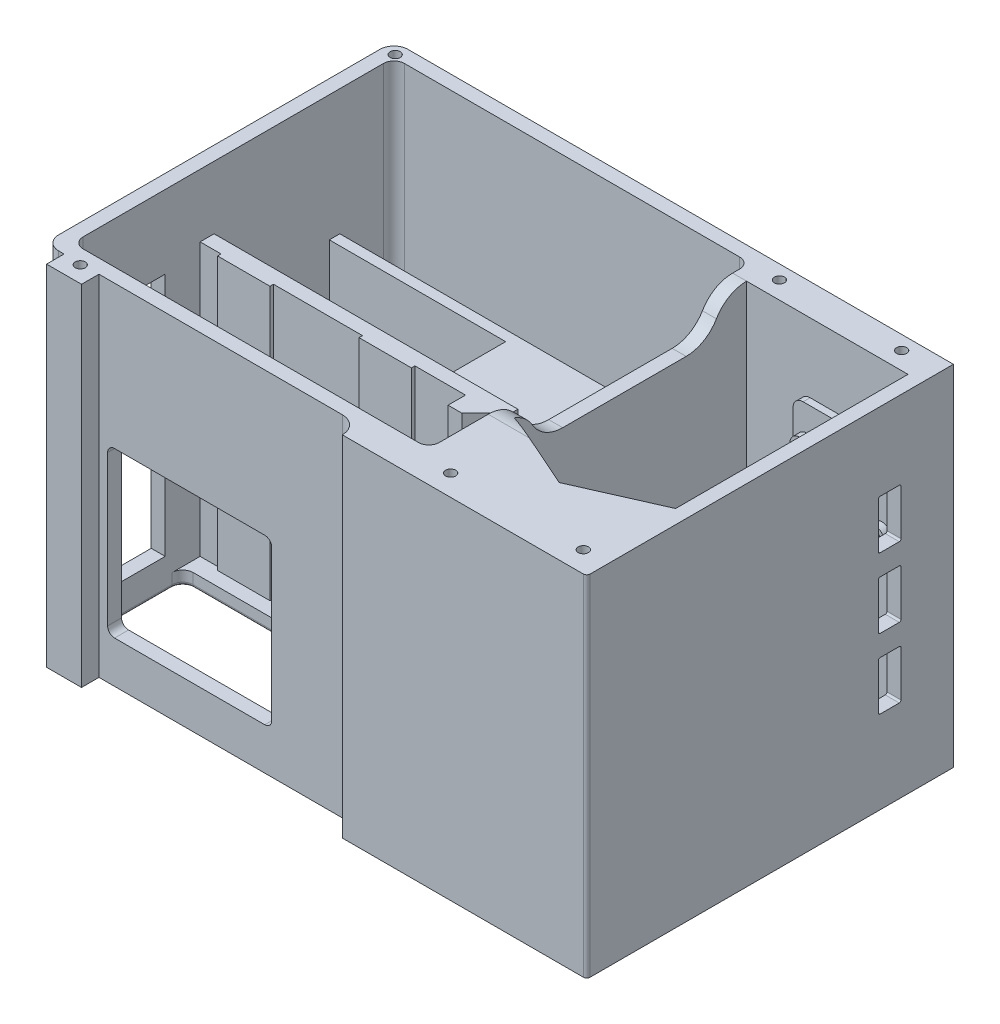
SolidWorks part; units mm, degrees
ref_plane "前视基准面" through (0, 0, 0) normal (0, 0, 1) x (1, 0, 0)
ref_plane "上视基准面" through (0, 0, 0) normal (0, 1, 0) x (1, 0, 0)
ref_plane "右视基准面" through (0, 0, 0) normal (1, 0, 0) x (0, 0, -1)
sketch "草图2" plane through (0, 0, 0) normal (0, 1, 0) x (1, 0, 0)
  line L1 (-51, 50) -> (51, 50)
  line L2 (-55, 46) -> (-55, -46)
  line L3 (-51, -50) -> (51, -50)
  line L4 (55, 46) -> (55, -46)
  line L5 (-55, 50) -> (55, -50) construction
  line L6 (-55, -50) -> (55, 50) construction
  arc A0 (51, 50) -> (55, 46) centre (51, 46) cw
  arc A1 (-55, -46) -> (-51, -50) centre (-51, -46) ccw
  arc A2 (-51, 50) -> (-55, 46) centre (-51, 46) ccw
  arc A3 (51, -50) -> (55, -46) centre (51, -46) ccw
  point P0 (0, 0)
  dimension "D3" = 4
  dimension "D1" = 100
  dimension "D2" = 110
extrude "凸台-拉伸1" add sketch "草图2" along normal blind 100
shell "抽壳1" thickness 4 removed face at (0, 100, 0)
sketch "草图3" plane through (0, 0, 0) normal (0, -1, 0) x (1, 0, 0)
  line L0 (-51, 50) -> (51, 50) construction
  line L1 (-48, 40) -> (11, 40)
  line L2 (-51, 37) -> (-51, 17.5)
  line L3 (-48, 14.5) -> (11, 14.5)
  line L4 (14, 37) -> (14, 17.5)
  line L5 (-55, -46) -> (-55, 46) construction
  arc A0 (11, 40) -> (14, 37) centre (11, 37) cw
  arc A1 (-51, 17.5) -> (-48, 14.5) centre (-48, 17.5) ccw
  arc A2 (11, 14.5) -> (14, 17.5) centre (11, 17.5) ccw
  arc A3 (-48, 40) -> (-51, 37) centre (-48, 37) ccw
  point P6 (14, 40)
  point P9 (-51, 14.5)
  point P14 (-51, 40)
  dimension "D3" = 3
  dimension "D1" = 25.5
  dimension "D2" = 65
  dimension "D4" = 10
  dimension "D5" = 4
extrude "切除-拉伸1" cut sketch "草图3" against normal up to next
sketch "草图4" plane through (0, 0, 0) normal (0, -1, 0) x (1, 0, 0)
  line L4 (11, 40) -> (46, 40)
  line L6 (11, 14.5) -> (46, 14.5)
  line L7 (49, 37) -> (49, 17.5)
  line L8 (55, 46) -> (55, -46) construction
  line L9 (14, 17.5) -> (14, 37) construction
  line L10 (14, 17.5) -> (14, 37)
  arc A0 (46, 40) -> (49, 37) centre (46, 37) cw
  arc A1 (46, 14.5) -> (49, 17.5) centre (46, 17.5) ccw
  arc A2 (14, 37) -> (11, 40) centre (11, 37) ccw construction
  arc A3 (14, 37) -> (11, 40) centre (11, 37) ccw
  arc A4 (11, 14.5) -> (14, 17.5) centre (11, 17.5) ccw construction
  arc A5 (11, 14.5) -> (14, 17.5) centre (11, 17.5) ccw
  dimension "D3" = 3
  dimension "D1" = 6
extrude "切除-拉伸2" cut sketch "草图4" against normal blind 2
sketch "草图5" plane through (0, 0, 0) normal (0, -1, 0) x (1, 0, 0)
  line L0 (3.5, -13) -> (48, -13)
  line L1 (-48, -13) -> (-3.5, -13)
  line L2 (-50, -15) -> (-50, -24.5)
  line L3 (-48, -26.5) -> (-3.5, -26.5)
  line L4 (-1.5, -15) -> (-1.5, -24.5)
  line L5 (1.5, -15) -> (1.5, -24.5)
  line L6 (3.5, -26.5) -> (48, -26.5)
  line L7 (50, -15) -> (50, -24.5)
  line L8 (-48, -31.5) -> (-3.5, -31.5)
  line L9 (-50, -33.5) -> (-50, -43)
  line L10 (-48, -45) -> (-3.5, -45)
  line L11 (-1.5, -33.5) -> (-1.5, -43)
  line L12 (3.5, -31.5) -> (48, -31.5)
  line L13 (1.5, -33.5) -> (1.5, -43)
  line L14 (3.5, -45) -> (48, -45)
  line L15 (50, -33.5) -> (50, -43)
  line L17 (51, -50) -> (-51, -50) construction
  line L18 (55, 46) -> (55, -46) construction
  line L21 (-55, -46) -> (-55, 46) construction
  arc A0 (48, -31.5) -> (50, -33.5) centre (48, -33.5) cw
  arc A1 (1.5, -43) -> (3.5, -45) centre (3.5, -43) ccw
  arc A2 (48, -45) -> (50, -43) centre (48, -43) ccw
  arc A3 (3.5, -31.5) -> (1.5, -33.5) centre (3.5, -33.5) ccw
  arc A4 (-3.5, -31.5) -> (-1.5, -33.5) centre (-3.5, -33.5) cw
  arc A5 (-50, -43) -> (-48, -45) centre (-48, -43) ccw
  arc A6 (-3.5, -45) -> (-1.5, -43) centre (-3.5, -43) ccw
  arc A7 (-48, -31.5) -> (-50, -33.5) centre (-48, -33.5) ccw
  arc A8 (48, -13) -> (50, -15) centre (48, -15) cw
  arc A9 (1.5, -24.5) -> (3.5, -26.5) centre (3.5, -24.5) ccw
  arc A10 (48, -26.5) -> (50, -24.5) centre (48, -24.5) ccw
  arc A11 (3.5, -13) -> (1.5, -15) centre (3.5, -15) ccw
  arc A12 (-3.5, -13) -> (-1.5, -15) centre (-3.5, -15) cw
  arc A13 (-50, -24.5) -> (-48, -26.5) centre (-48, -24.5) ccw
  arc A14 (-3.5, -26.5) -> (-1.5, -24.5) centre (-3.5, -24.5) ccw
  arc A15 (-48, -13) -> (-50, -15) centre (-48, -15) ccw
  point P42 (-1.5, -13)
  point P45 (-50, -26.5)
  point P50 (-50, -13)
  dimension "D3" = 2
  dimension "D1" = 13.5
  dimension "D2" = 48.5
  dimension "D4" = 5
  dimension "D5" = 5
  dimension "D6" = 5
  dimension "D7" = 5
extrude "切除-拉伸3" cut sketch "草图5" against normal up to next
fillet "圆角1" radius 3 4 edges at (-51, 52, -46) (-51, 52, 46) (51, 52, 46) (51, 52, -46)
sketch "草图6" plane through (0, 4, 0) normal (0, 1, 0) x (1, 0, 0)
  line L0 (51, -43) -> (51, 43) construction
  line L1 (-51, -5.5) -> (51, -5.5)
  line L2 (-51, -5.5) -> (-51, -9.5)
  line L3 (-51, -9.5) -> (51, -9.5)
  line L4 (51, -5.5) -> (51, -9.5)
  line L5 (-51, 43) -> (-51, -43) construction
  line L7 (-48, -46) -> (48, -46) construction
  dimension "D1" = 4
  dimension "D2" = 0
  dimension "D3" = 0
  dimension "D4" = 36.5
extrude "凸台-拉伸2" add sketch "草图6" along normal blind 78
sketch "草图7" plane through (0, 4, 0) normal (0, 1, 0) x (1, 0, 0)
  line L0 (-51, -9.5) -> (51, -9.5) construction
  line L1 (-30, -9.5) -> (-45, -9.5)
  line L2 (-30, -9.5) -> (-30, -10.5)
  line L3 (-30, -10.5) -> (-45, -10.5)
  line L4 (-45, -9.5) -> (-45, -10.5)
  line L6 (-48, -46) -> (48, -46) construction
  line L7 (-51, 43) -> (-51, -43) construction
  dimension "D1" = 35.5
  dimension "D2" = 15
  dimension "D3" = 6
extrude "凸台-拉伸3" add sketch "草图7" along normal up to surface (78 mm away) up to face at (0, 82, 7.5)
sketch "草图9" plane through (0, 4, 0) normal (0, 1, 0) x (1, 0, 0)
  line L0 (-30, -9.5) -> (51, -9.5) construction
  line L1 (10.5, -9.5) -> (-4.5, -9.5)
  line L2 (10.5, -9.5) -> (10.5, -10.5)
  line L3 (10.5, -10.5) -> (-4.5, -10.5)
  line L4 (-4.5, -9.5) -> (-4.5, -10.5)
  line L5 (-45, -10.5) -> (-30, -10.5) construction
  dimension "D1" = 15
extrude "凸台-拉伸4" add sketch "草图9" along normal up to surface (78 mm away) up to face at (-18.75, 82, 8.75)
sketch "草图10" plane through (0, 4, 0) normal (0, 1, 0) x (1, 0, 0)
  line L0 (10.5, -9.5) -> (51, -9.5) construction
  line L1 (29, -9.5) -> (25, -9.5)
  line L3 (29, -14.5) -> (25, -14.5)
  line L4 (25, -9.5) -> (25, -14.5)
  line L5 (-51, 43) -> (-51, -43) construction
  line L6 (29, -14.5) -> (34, -9.5)
  line L7 (34, -9.5) -> (29, -9.5)
  dimension "D1" = 76
  dimension "D2" = 5
  dimension "D3" = 4
extrude "凸台-拉伸5" add sketch "草图10" along normal up to surface (78 mm away) up to face at (-11.5, 82, 9.1667)
sketch "草图13" plane through (0, 0, 5.5) normal (0, 0, -1) x (-1, 0, 0)
  line L0 (-36, 82) -> (-36, 62)
  line L1 (-36, 62) -> (-51, 62)
  line L4 (-51, 4) -> (51, 4)
  line L5 (51, 4) -> (51, 82)
  line L6 (51, 82) -> (-51, 82)
  line L7 (-51, 82) -> (-51, 4)
  line L10 (-36, 82) -> (-51, 82)
  line L11 (-51, 82) -> (-51, 62)
  dimension "D2" = 15
  dimension "D3" = 20
  dimension "D1" = 0
extrude "切除-拉伸4" cut sketch "草图13" against normal up to next
sketch "草图15" plane through (0, 4, 0) normal (0, 1, 0) x (1, 0, 0)
  line L0 (-51, 43) -> (-51, -43) construction
  line L1 (-51, 30.5) -> (52.1172, 30.5)
  line L2 (-51, 30.5) -> (-51, 27.5)
  line L3 (-51, 27.5) -> (52.1172, 27.5)
  line L4 (52.1172, 30.5) -> (52.1172, 27.5)
  line L5 (48, 46) -> (-48, 46) construction
  line L7 (48, 26.5) -> (3.5, 26.5) construction
  dimension "D1" = 15.5
  dimension "D2" = 1
extrude "凸台-拉伸7" add sketch "草图15" along normal blind 60
sketch "草图16" plane through (0, 4, 0) normal (0, 1, 0) x (1, 0, 0)
  line L6 (36, -5.5) -> (-51, -5.5) construction
  line L7 (-0.5, -5.5) -> (1.5, -5.5)
  line L8 (-0.5, -5.5) -> (-0.5, 27.5)
  line L9 (-0.5, 27.5) -> (1.5, 27.5)
  line L10 (1.5, -5.5) -> (1.5, 27.5)
  line L11 (-51, 27.5) -> (51, 27.5) construction
  line L12 (-51, 43) -> (-51, -43) construction
  line L13 (1.5, 24.5) -> (1.5, 15) construction
  dimension "D1" = 50.5
extrude "凸台-拉伸8" add sketch "草图16" along normal up to surface (60 mm away) up to face at (0, 64, -29)
sketch "草图17" plane through (0, 4, 0) normal (0, 1, 0) x (1, 0, 0)
  line L0 (-0.5, 27.5) -> (-0.5, -5.5) construction
  line L1 (-51, -5.5) -> (-0.5, -5.5)
  line L2 (-51, -5.5) -> (-51, 11.6)
  line L3 (-51, 11.6) -> (-0.5, 11.6)
  line L4 (-0.5, -5.5) -> (-0.5, 11.6)
  line L5 (-51, 27.5) -> (-0.5, 27.5) construction
  dimension "D1" = 15.9
extrude "凸台-拉伸9" add sketch "草图17" along normal up to surface (60 mm away) up to face at (0.25, 64, -20)
sketch "草图18" plane through (0, 0, 50) normal (0, 0, 1) x (1, 0, 0)
  line L0 (-55, 100) -> (-55, 0) construction
  line L1 (-35, 59) -> (8, 59)
  line L2 (-37, 57) -> (-37, 14)
  line L3 (-35, 12) -> (8, 12)
  line L4 (10, 57) -> (10, 14)
  line L5 (-51, 0) -> (51, 0) construction
  arc A0 (8, 59) -> (10, 57) centre (8, 57) cw
  arc A1 (-37, 14) -> (-35, 12) centre (-35, 14) ccw
  arc A2 (8, 12) -> (10, 14) centre (8, 14) ccw
  arc A3 (-35, 59) -> (-37, 57) centre (-35, 57) ccw
  point P10 (10, 59)
  point P15 (10, 12)
  point P18 (-37, 59)
  dimension "D5" = 2
  dimension "D1" = 47
  dimension "D2" = 47
  dimension "D3" = 18
  dimension "D4" = 12
extrude "切除-拉伸5" cut sketch "草图18" against normal up to next
sketch "草图19" plane through (-55, 0, 0) normal (-1, 0, 0) x (0, 0, 1)
  line L1 (19.5, 9) -> (41.5, 9)
  line L2 (19.5, 9) -> (19.5, 79)
  line L3 (19.5, 79) -> (41.5, 79)
  line L4 (41.5, 9) -> (41.5, 79)
  line L5 (-46, 0) -> (46, 0) construction
  line L7 (50, 100) -> (50, 0) construction
  dimension "D1" = 70
  dimension "D2" = 22
  dimension "D3" = 9
  dimension "D4" = 8.5
extrude "切除-拉伸6" cut sketch "草图19" against normal up to next
sketch "草图20" plane through (0, 4, 0) normal (0, 1, 0) x (1, 0, 0)
  line L0 (-48, -46) -> (48, -46) construction
  line L1 (12.1183, -46) -> (18.3326, -46)
  line L2 (12.1183, -46) -> (12.1183, -44.4)
  line L3 (12.1183, -44.4) -> (18.3326, -44.4)
  line L4 (18.3326, -46) -> (18.3326, -44.4)
  line L6 (-48, -46) -> (-43.8248, -46)
  line L7 (-48, -46) -> (-48, -44.4)
  line L8 (-48, -44.4) -> (-43.8248, -44.4)
  line L9 (-43.8248, -46) -> (-43.8248, -44.4)
  line L13 (-4.5, -10.5) -> (10.5, -10.5) construction
  line L14 (-45, -10.5) -> (-30, -10.5) construction
  dimension "D1" = 33.9
  dimension "D2" = 33.9
extrude "凸台-拉伸10" add sketch "草图20" along normal up to surface (78 mm away) up to face at (-3.4375, 82, 9.875)
sketch "草图21" plane through (0, 4, 0) normal (0, 1, 0) x (1, 0, 0)
  line L0 (1.5, 11.6) -> (51, 11.6)
  line L1 (1.5, -5.5) -> (1.5, 27.5) construction
  line L2 (1.5, -5.5) -> (1.5, 27.5)
  line L3 (36, -5.5) -> (-51, -5.5) construction
  line L4 (36, -5.5) -> (1.5, -5.5)
  line L5 (51, -5.5) -> (1.5, -5.5) construction
  line L6 (51, -5.5) -> (1.5, -5.5)
  line L7 (51, -5.5) -> (51, 27.5) construction
  line L8 (1.5, 15) -> (1.5, -5.5)
  line L9 (1.5, -5.5) -> (51, -5.5)
  line L10 (51, -5.5) -> (51, 27.5)
  line L11 (51, 27.5) -> (1.5, 27.5)
  line L12 (1.5, 27.5) -> (1.5, 24.5)
  line L13 (3.5, 26.5) -> (48, 26.5)
  line L14 (50, 24.5) -> (50, 15)
  line L15 (48, 13) -> (3.5, 13)
  line L16 (1.5, 15) -> (1.5, 11.6)
  line L18 (51, 11.6) -> (51, 27.5)
  line L19 (51, 27.5) -> (1.5, 27.5)
  line L20 (1.5, 27.5) -> (1.5, 24.5)
  line L21 (3.5, 26.5) -> (48, 26.5)
  line L22 (50, 24.5) -> (50, 15)
  line L23 (48, 13) -> (3.5, 13)
  line L24 (51, -5.5) -> (51, 27.5)
  arc A4 (3.5, 26.5) -> (1.5, 24.5) centre (3.5, 24.5) ccw
  arc A5 (50, 24.5) -> (48, 26.5) centre (48, 24.5) ccw
  arc A6 (48, 13) -> (50, 15) centre (48, 15) ccw
  arc A7 (1.5, 15) -> (3.5, 13) centre (3.5, 15) ccw
  arc A8 (3.5, 26.5) -> (1.5, 24.5) centre (3.5, 24.5) ccw
  arc A9 (50, 24.5) -> (48, 26.5) centre (48, 24.5) ccw
  arc A10 (48, 13) -> (50, 15) centre (48, 15) ccw
  arc A11 (1.5, 15) -> (3.5, 13) centre (3.5, 15) ccw
  line M14 (1.5, 15) -> (1.5, -5.5)
  line M15 (1.5, -5.5) -> (51, -5.5)
  line M16 (51, -5.5) -> (51, 27.5)
  line M17 (51, 27.5) -> (1.5, 27.5)
  line M18 (1.5, 27.5) -> (1.5, 24.5)
  arc M19 (1.5, 24.5) -> (3.5, 26.5) centre (3.5, 24.5) cw
  line M20 (3.5, 26.5) -> (48, 26.5)
  arc M21 (48, 26.5) -> (50, 24.5) centre (48, 24.5) cw
  line M22 (50, 24.5) -> (50, 15)
  arc M23 (50, 15) -> (48, 13) centre (48, 15) cw
  line M24 (48, 13) -> (3.5, 13)
  arc M25 (3.5, 13) -> (1.5, 15) centre (3.5, 15) cw
  dimension "D1" = 0
extrude "凸台-拉伸11" add sketch "草图21" along normal up to surface (60 mm away) contours L0 M14 M15 M16 | L0 M14 M16 M17 M18 M19 M20 M21 M22 M23 M24 M25 region at (2.0199, 4, -13.3) region at (26.25, 4, -3.05) up to face at (-10, 64, -18.32)
fillet "圆角2" radius 3 1 edges at (43.5, 62, 5.5)
fillet "圆角3" radius 3 1 edges at (43.5, 64, 5.5)
sketch "草图22" plane through (0, 0, 0) normal (0, -1, 0) x (1, 0, 0)
  line L0 (51, 50) -> (105.215, 50)
  line L1 (105.215, 50) -> (105.215, -50)
  line L2 (105.215, -50) -> (51, -50)
  line L4 (55, -46) -> (55, 46)
  line L5 (51, 50) -> (-51, 50)
  line L6 (-55, 46) -> (-55, -46)
  line L7 (-51, -50) -> (51, -50)
  line L8 (55, -46) -> (55, 46)
  arc A4 (51, -50) -> (55, -46) centre (51, -46) ccw
  arc A5 (55, 46) -> (51, 50) centre (51, 46) ccw
  arc A6 (-51, 50) -> (-55, 46) centre (-51, 46) ccw
  arc A7 (-55, -46) -> (-51, -50) centre (-51, -46) ccw
  arc A8 (51, -50) -> (55, -46) centre (51, -46) ccw
  arc A9 (55, 46) -> (51, 50) centre (51, 46) ccw
  dimension "D1" = 0
extrude "凸台-拉伸12" add sketch "草图22" against normal up to surface (100 mm away) up to face at (0, 100, 0)
sketch "草图23" plane through (0, 0, 0) normal (0, -1, 0) x (1, 0, 0)
  line L5 (-51, 50) -> (105.215, 50) construction
  line L6 (105.215, 50) -> (35.215, 50)
  line L7 (105.215, 50) -> (105.215, 55)
  line L8 (105.215, 55) -> (35.215, 55)
  line L9 (35.215, 50) -> (35.215, 55)
  line L10 (-49.4681, 50) -> (-39.4681, 50)
  line L11 (-49.4681, 50) -> (-49.4681, 55)
  line L12 (-49.4681, 55) -> (-39.4681, 55)
  line L13 (-39.4681, 50) -> (-39.4681, 55)
  dimension "D1" = 70
  dimension "D2" = 5
  dimension "D3" = 5
  dimension "D4" = 10
extrude "凸台-拉伸13" add sketch "草图23" against normal up to surface (100 mm away) up to face at (-0.5378, 100, 0)
fillet "圆角5" radius 1 5 edges at (28.5, 2, 14.5) (28.5, 2, 40) (48.1213, 2, 39.1213) (49, 2, 27.25) (48.1213, 2, 15.3787)
fillet "圆角6" radius 1 8 edges at (-1, 0, 14.5) (-50.1213, 0, 15.3787) (-51, 0, 27.25) (-50.1213, 0, 39.1213) (-1, 0, 40) (48.1213, 0, 39.1213) (49, 0, 27.25) (48.1213, 0, 15.3787)
fillet "圆角7" radius 1 24 edges at (-2.0858, 0, -44.4142) (-25.75, 0, -45) (-49.4142, 0, -44.4142) (-50, 0, -38.25) (-49.4142, 0, -32.0858) (-25.75, 0, -31.5) (-2.0858, 0, -32.0858) (2.0858, 0, -32.0858) (25.75, 0, -31.5) (49.4142, 0, -32.0858) (50, 0, -38.25) (49.4142, 0, -44.4142) (25.75, 0, -45) (2.0858, 0, -44.4142) (-2.0858, 0, -25.9142) (-25.75, 0, -26.5) (-49.4142, 0, -25.9142) (-50, 0, -19.75) (-49.4142, 0, -13.5858) (-25.75, 0, -13) (-2.0858, 0, -13.5858) (-1.5, 0, -38.25) (1.5, 0, -38.25) (-1.5, 0, -19.75)
sketch "草图24" plane through (0, 100, 0) normal (0, 1, 0) x (1, 0, 0)
  line L0 (-48, -46) -> (48, -46) construction
  line L1 (55, 46) -> (101.215, 46)
  line L2 (55, 46) -> (55, -46)
  line L3 (55, -46) -> (101.215, -46)
  line L4 (101.215, 46) -> (101.215, -46)
  line L5 (105.215, -55) -> (105.215, 50) construction
  line L6 (105.215, 50) -> (-51, 50) construction
  line L7 (51, -43) -> (51, 43) construction
  dimension "D1" = 4
  dimension "D2" = 4
  dimension "D3" = 4
extrude "切除-拉伸7" cut sketch "草图24" against normal offset from surface (96 mm away) 4 up to face at (-25.75, 0, -38.25)
sketch "草图25" plane through (0, 4, 0) normal (0, 1, 0) x (1, 0, 0)
  line L0 (101.215, 41) -> (55, 41)
  line L4 (55, 46) -> (55, -46)
  line L5 (55, -46) -> (101.215, -46)
  line L6 (101.215, -46) -> (101.215, 46)
  line L7 (101.215, 46) -> (55, 46)
  line L8 (55, 46) -> (55, -46)
  line L9 (55, -46) -> (101.215, -46)
  line L10 (101.215, -46) -> (101.215, 46)
  line L11 (101.215, 46) -> (55, 46)
  line M6 (55, 46) -> (55, -46)
  line M8 (101.215, -46) -> (101.215, 46)
  line M9 (101.215, 46) -> (55, 46)
  dimension "D2" = 5
  dimension "D1" = 0
extrude "凸台-拉伸14" add sketch "草图25" along normal up to surface (96 mm away) contours L0 M8 M9 M6 region at (78.1075, 4, -43.5) up to face at (78.1075, 100, 0)
sketch "草图27" plane through (0, 0, 0) normal (0, -1, 0) x (1, 0, 0)
  line L0 (76.2954, -28.5) -> (89.2954, -28.5) construction
  line L1 (76.2954, -28.5) -> (89.2954, -28.5)
  line L2 (89.7954, -29) -> (89.7954, -34.5) construction
  line L3 (89.7954, -29) -> (89.7954, -34.5)
  line L4 (89.2954, -35) -> (76.2954, -35) construction
  line L5 (89.2954, -35) -> (76.2954, -35)
  line L14 (75.7954, -34.5) -> (75.7954, -29) construction
  line L15 (75.7954, -34.5) -> (75.7954, -29)
  arc A0 (89.7954, -29) -> (89.2954, -28.5) centre (89.2954, -29) ccw construction
  arc A1 (89.7954, -29) -> (89.2954, -28.5) centre (89.2954, -29) ccw
  arc A2 (89.2954, -35) -> (89.7954, -34.5) centre (89.2954, -34.5) ccw construction
  arc A3 (89.2954, -35) -> (89.7954, -34.5) centre (89.2954, -34.5) ccw
  arc A4 (75.7954, -34.5) -> (76.2954, -35) centre (76.2954, -34.5) ccw construction
  arc A5 (75.7954, -34.5) -> (76.2954, -35) centre (76.2954, -34.5) ccw
  arc A6 (76.2954, -28.5) -> (75.7954, -29) centre (76.2954, -29) ccw construction
  arc A7 (76.2954, -28.5) -> (75.7954, -29) centre (76.2954, -29) ccw
extrude "切除-拉伸8" cut sketch "草图27" against normal blind 19 and the other way blind 38
sketch "草图28" plane through (105.215, 0, 0) normal (1, 0, 0) x (0, 0, -1)
  line L0 (35, 64.2517) -> (35, 77.2517) construction
  line L1 (35, 64.2517) -> (35, 77.2517)
  line L2 (34.5, 77.7517) -> (29, 77.7517) construction
  line L3 (34.5, 77.7517) -> (29, 77.7517)
  line L12 (28.5, 64.2517) -> (28.5, 77.2517) construction
  line L13 (28.5, 64.2517) -> (28.5, 77.2517)
  line L14 (34.5, 63.7517) -> (29, 63.7517) construction
  line L15 (34.5, 63.7517) -> (29, 63.7517)
  line L16 (35, 44.2516) -> (35, 57.2517) construction
  line L17 (35, 44.2516) -> (35, 57.2517)
  line L18 (34.5, 57.7517) -> (29, 57.7517) construction
  line L19 (34.5, 57.7517) -> (29, 57.7517)
  line L20 (28.5, 44.2516) -> (28.5, 57.2517) construction
  line L21 (28.5, 44.2516) -> (28.5, 57.2517)
  line L22 (34.5, 43.7516) -> (29, 43.7516) construction
  line L23 (34.5, 43.7516) -> (29, 43.7516)
  line L24 (35, 24.2516) -> (35, 37.2516) construction
  line L25 (35, 24.2516) -> (35, 37.2516)
  line L26 (34.5, 37.7516) -> (29, 37.7516) construction
  line L27 (34.5, 37.7516) -> (29, 37.7516)
  line L28 (28.5, 24.2516) -> (28.5, 37.2516) construction
  line L29 (28.5, 24.2516) -> (28.5, 37.2516)
  line L30 (34.5, 23.7516) -> (29, 23.7516) construction
  line L31 (34.5, 23.7516) -> (29, 23.7516)
  arc A0 (35, 77.2517) -> (34.5, 77.7517) centre (34.5, 77.2517) ccw construction
  arc A1 (35, 77.2517) -> (34.5, 77.7517) centre (34.5, 77.2517) ccw
  arc A2 (29, 77.7517) -> (28.5, 77.2517) centre (29, 77.2517) ccw construction
  arc A3 (29, 77.7517) -> (28.5, 77.2517) centre (29, 77.2517) ccw
  arc A4 (34.5, 63.7517) -> (35, 64.2517) centre (34.5, 64.2517) ccw construction
  arc A5 (34.5, 63.7517) -> (35, 64.2517) centre (34.5, 64.2517) ccw
  arc A6 (28.5, 64.2517) -> (29, 63.7517) centre (29, 64.2517) ccw construction
  arc A7 (28.5, 64.2517) -> (29, 63.7517) centre (29, 64.2517) ccw
  arc A8 (35, 57.2517) -> (34.5, 57.7517) centre (34.5, 57.2517) ccw construction
  arc A9 (35, 57.2517) -> (34.5, 57.7517) centre (34.5, 57.2517) ccw
  arc A10 (29, 57.7517) -> (28.5, 57.2517) centre (29, 57.2517) ccw construction
  arc A11 (29, 57.7517) -> (28.5, 57.2517) centre (29, 57.2517) ccw
  arc A12 (34.5, 43.7516) -> (35, 44.2516) centre (34.5, 44.2516) ccw construction
  arc A13 (34.5, 43.7516) -> (35, 44.2516) centre (34.5, 44.2516) ccw
  arc A14 (28.5, 44.2516) -> (29, 43.7516) centre (29, 44.2516) ccw construction
  arc A15 (28.5, 44.2516) -> (29, 43.7516) centre (29, 44.2516) ccw
  arc A16 (35, 37.2516) -> (34.5, 37.7516) centre (34.5, 37.2516) ccw construction
  arc A17 (35, 37.2516) -> (34.5, 37.7516) centre (34.5, 37.2516) ccw
  arc A18 (29, 37.7516) -> (28.5, 37.2516) centre (29, 37.2516) ccw construction
  arc A19 (29, 37.7516) -> (28.5, 37.2516) centre (29, 37.2516) ccw
  arc A20 (34.5, 23.7516) -> (35, 24.2516) centre (34.5, 24.2516) ccw construction
  arc A21 (34.5, 23.7516) -> (35, 24.2516) centre (34.5, 24.2516) ccw
  arc A22 (28.5, 24.2516) -> (29, 23.7516) centre (29, 24.2516) ccw construction
  arc A23 (28.5, 24.2516) -> (29, 23.7516) centre (29, 24.2516) ccw
extrude "切除-拉伸9" cut sketch "草图28" along normal blind 50 and the other way blind 29
sketch "草图30" plane through (0, 0, -41) normal (0, 0, 1) x (1, 0, 0)
  line L12 (101.2231, 77.2857) -> (101.2231, 4.0081)
  line L13 (70.2838, 77.2857) -> (70.2838, 4.0081)
  line L14 (70.2838, 4.0081) -> (101.2231, 4.0081)
  line L15 (73.1838, 80.1857) -> (98.3231, 80.1857)
  arc A0 (98.3231, 80.1857) -> (101.2231, 77.2857) centre (98.3231, 77.2857) cw
  arc A1 (73.1838, 80.1857) -> (70.2838, 77.2857) centre (73.1838, 77.2857) ccw
extrude "凸台-拉伸15" add sketch "草图30" along normal up to surface (2 mm away)
sketch "草图31" plane through (0, 0, -39) normal (0, 0, 1) x (1, 0, 0)
  circle A0 centre (74.1954, 70.1178) radius 2.8 construction
  circle A1 centre (74.1954, 70.1178) radius 2.8
  circle A2 centre (74.1954, 70.1178) radius 1.7 construction
  circle A3 centre (74.1954, 70.1178) radius 1.7
  circle A4 centre (95.7144, 58.8106) radius 2.9 construction
  circle A5 centre (95.7144, 58.8106) radius 2.9
  circle A6 centre (95.7144, 58.8106) radius 1.7 construction
  circle A7 centre (95.7144, 58.8106) radius 1.7
  circle A8 centre (95.1954, 9.3516) radius 1.7 construction
  circle A9 centre (95.1954, 9.3516) radius 1.7
  circle A10 centre (95.1954, 9.3516) radius 2.8 construction
  circle A11 centre (95.1954, 9.3516) radius 2.8
  circle A12 centre (74.1954, 9.3516) radius 2.8 construction
  circle A13 centre (74.1954, 9.3516) radius 2.8
  circle A14 centre (74.1954, 9.3516) radius 1.7 construction
  circle A15 centre (74.1954, 9.3516) radius 1.7
extrude "凸台-拉伸16" add sketch "草图31" along normal up to surface (2 mm away)
fillet "圆角8" radius 1 1 edges at (105.215, 50, 55)
fillet "圆角9" radius 5 1 edges at (35.215, 50, 50)
sketch "草图32" plane through (0, 64, 0) normal (0, 1, 0) x (1, 0, 0)
  line L0 (1.5, 15) -> (1.5, 24.5) construction
  line L1 (1.5, 15) -> (1.5, 24.5)
  line L2 (48, 13) -> (3.5, 13) construction
  line L3 (48, 13) -> (3.5, 13)
  line L4 (3.5, 26.5) -> (48, 26.5) construction
  line L5 (3.5, 26.5) -> (48, 26.5)
  line L6 (50, 24.5) -> (50, 15) construction
  line L7 (50, 24.5) -> (50, 15)
  arc A0 (1.5, 15) -> (3.5, 13) centre (3.5, 15) ccw construction
  arc A1 (1.5, 15) -> (3.5, 13) centre (3.5, 15) ccw
  arc A2 (3.5, 26.5) -> (1.5, 24.5) centre (3.5, 24.5) ccw construction
  arc A3 (3.5, 26.5) -> (1.5, 24.5) centre (3.5, 24.5) ccw
  arc A4 (50, 24.5) -> (48, 26.5) centre (48, 24.5) ccw construction
  arc A5 (50, 24.5) -> (48, 26.5) centre (48, 24.5) ccw
  arc A6 (48, 13) -> (50, 15) centre (48, 15) ccw construction
  arc A7 (48, 13) -> (50, 15) centre (48, 15) ccw
extrude "凸台-拉伸17" add sketch "草图32" against normal blind 30
sketch "草图34" plane through (0, 34, 0) normal (0, -1, 0) x (1, 0, 0)
  line L0 (44, -13) -> (44, -26.5)
  line L4 (1.5, -15) -> (1.5, -24.5)
  line L5 (3.5, -26.5) -> (48, -26.5)
  line L6 (50, -24.5) -> (50, -15)
  line L7 (48, -13) -> (3.5, -13)
  line L8 (1.5, -15) -> (1.5, -24.5)
  line L9 (3.5, -26.5) -> (48, -26.5)
  line L10 (50, -24.5) -> (50, -15)
  line L11 (48, -13) -> (3.5, -13)
  arc A4 (3.5, -13) -> (1.5, -15) centre (3.5, -15) ccw
  arc A5 (1.5, -24.5) -> (3.5, -26.5) centre (3.5, -24.5) ccw
  arc A6 (48, -26.5) -> (50, -24.5) centre (48, -24.5) ccw
  arc A7 (50, -15) -> (48, -13) centre (48, -15) ccw
  arc A8 (3.5, -13) -> (1.5, -15) centre (3.5, -15) ccw
  arc A9 (1.5, -24.5) -> (3.5, -26.5) centre (3.5, -24.5) ccw
  arc A10 (48, -26.5) -> (50, -24.5) centre (48, -24.5) ccw
  arc A11 (50, -15) -> (48, -13) centre (48, -15) ccw
  line M13 (3.5, -26.5) -> (48, -26.5)
  arc M14 (48, -26.5) -> (50, -24.5) centre (48, -24.5) ccw
  line M15 (50, -24.5) -> (50, -15)
  arc M16 (50, -15) -> (48, -13) centre (48, -15) ccw
  line M17 (48, -13) -> (3.5, -13)
  dimension "D2" = 6
  dimension "D1" = 0
extrude "切除-拉伸11" cut sketch "草图34" against normal blind 65 contours L0 M17 M13 M14 M15 M16 region at (46.9447, 34, -19.75)
sketch "草图36" plane through (0, 4, 0) normal (0, 1, 0) x (1, 0, 0)
  line L0 (101.215, -46) -> (55, -25.5512)
  line L1 (55, 41) -> (55, -46) construction
  line L2 (55, -46) -> (101.215, -25.5512)
  line L3 (101.215, -46) -> (101.215, 41) construction
  line L4 (55, -46) -> (101.215, -46) construction
  line L5 (55, -46) -> (101.215, -46)
  line L6 (101.215, -46) -> (101.215, 41)
  line L7 (55, 41) -> (55, -46)
  line M1 (101.215, -46) -> (101.215, 41)
  line M3 (55, 41) -> (55, -46)
  line M4 (55, -46) -> (101.215, -46)
extrude "凸台-拉伸18" add sketch "草图36" along direction (0, -1, 0) on the side of the normal up to surface (96 mm away) contours L2 L0 M1 | L2 L0 M4 | L2 L0 M3 region at (78.1075, 4, 42.5919) region at (93.5125, 4, 35.7756) region at (62.7025, 4, 35.7756) up to face at (78.1075, 100, 2.5)
sketch "草图37" plane through (0, 100, 0) normal (0, 1, 0) x (1, 0, 0)
  line L0 (105.215, -54) -> (105.215, 50) construction
  line L1 (-49.4681, -50) -> (-49.4681, -55) construction
  line L2 (55, 41) -> (101.215, 41) construction
  line L3 (101.215, 41) -> (55, 41) construction
  point P0 (98.215, -48.978)
  point P1 (60.215, -48.978)
  point P2 (94.3916, 46)
  point P3 (59.3916, 46)
  point P4 (-44.4681, -50.3601)
  point P14 (-51.5198, 46.8795)
  dimension "D1" = 7
  dimension "D2" = 38
  dimension "D3" = 5
  dimension "D4" = 5
  dimension "D5" = 5
  dimension "D6" = 35
hole_wizard "M3.5 螺纹孔1" positions "草图37" profile "草图38" tap size "M3.5" standard "GB"
sketch "草图38" plane through (98.215, 100, 48.978) normal (1, 0, 0) x (0, 0, 1)
  line L0 (0, 0) -> (0, 10)
  line L1 (0, 10) -> (1.45, 9.1288)
  line L2 (1.45, 9.1288) -> (1.45, 0)
  line L5 (1.45, 0) -> (0, 0)
  line L10 (0, 10) -> (-1.45, 9.1288) construction
  line L11 (0, -6.35) -> (0, 107.95) construction
  dimension "螺纹孔钻头直径" = 2.9
  dimension "螺纹孔钻头深度" = 10
  dimension "导头角度" = 118
cosmetic thread "孔螺蚊线1" parameters "D1"=7, "D2"=3.5
cosmetic thread "孔螺蚊线2" parameters "D1"=7, "D2"=3.5
cosmetic thread "孔螺蚊线3" parameters "D1"=7, "D2"=3.5
cosmetic thread "孔螺蚊线4" parameters "D1"=7, "D2"=3.5
cosmetic thread "孔螺蚊线5" parameters "D1"=7, "D2"=3.5
cosmetic thread "孔螺蚊线6" parameters "D1"=7, "D2"=3.5
sketch "草图39" plane through (51, 0, 0) normal (-1, 0, 0) x (0, 0, 1)
  line L0 (43, 100) -> (-43, 100) construction
  line L1 (-31, 100) -> (19, 100)
  line L2 (-31, 100) -> (-31, 90)
  line L3 (-31, 90) -> (19, 90)
  line L4 (19, 100) -> (19, 90)
  line L5 (-46, 4) -> (-46, 100) construction
  dimension "D1" = 50
  dimension "D2" = 10
  dimension "D3" = 15
extrude "切除-拉伸12" cut sketch "草图39" against normal blind 23
fillet "圆角10" radius 10 2 edges at (53, 100, 19) (53, 100, -31)
fillet "圆角11" radius 10 2 edges at (53, 90, -31) (53, 90, 19)
sketch "草图40" plane through (0, 34, 0) normal (0, -1, 0) x (1, 0, 0)
  line L4 (44, -26.5) -> (44, -13)
  line L5 (44, -13) -> (3.5, -13)
  line L6 (1.5, -15) -> (1.5, -24.5)
  line L7 (3.5, -26.5) -> (44, -26.5)
  line L8 (44, -26.5) -> (44, -13)
  line L9 (44, -13) -> (3.5, -13)
  line L10 (1.5, -15) -> (1.5, -24.5)
  line L11 (3.5, -26.5) -> (44, -26.5)
  arc A2 (3.5, -13) -> (1.5, -15) centre (3.5, -15) ccw
  arc A3 (1.5, -24.5) -> (3.5, -26.5) centre (3.5, -24.5) ccw
  arc A4 (3.5, -13) -> (1.5, -15) centre (3.5, -15) ccw
  arc A5 (1.5, -24.5) -> (3.5, -26.5) centre (3.5, -24.5) ccw
  dimension "D1" = 0
extrude "切除-拉伸13" cut sketch "草图40" against normal blind 15
sketch "草图41" plane through (0, 64, 0) normal (0, 1, 0) x (1, 0, 0)
  line L6 (48, 26.5) -> (44, 26.5) construction
  line L7 (48, 26.5) -> (44, 26.5)
  line L8 (50, 15) -> (50, 24.5) construction
  line L9 (50, 15) -> (50, 24.5)
  line L10 (44, 13) -> (48, 13) construction
  line L11 (44, 13) -> (48, 13)
  line L12 (44, 26.5) -> (44, 13) construction
  line L13 (44, 26.5) -> (44, 13)
  arc A0 (50, 24.5) -> (48, 26.5) centre (48, 24.5) ccw construction
  arc A1 (50, 24.5) -> (48, 26.5) centre (48, 24.5) ccw
  arc A2 (48, 13) -> (50, 15) centre (48, 15) ccw construction
  arc A3 (48, 13) -> (50, 15) centre (48, 15) ccw
extrude "凸台-拉伸19" add sketch "草图41" against normal up to surface (15 mm away) up to face at (16.1953, 49, -19.75)
sketch "草图42" plane through (0, 49, 0) normal (0, -1, 0) x (1, 0, 0)
  line L0 (36.9466, -23) -> (36.9466, -13) construction
  line L1 (36.9466, -23) -> (36.9466, -13)
  line L2 (44.9466, -23) -> (44.9466, -13) construction
  line L3 (44.9466, -23) -> (44.9466, -13)
  line L5 (36.9466, -13) -> (44.9466, -13)
  line L6 (3.5, -26.5) -> (48, -26.5) construction
  line L8 (36.9466, -23) -> (36.9466, -26.5)
  line L9 (36.9466, -26.5) -> (44.9466, -26.5)
  line L10 (44.9466, -23) -> (44.9466, -26.5)
extrude "切除-拉伸15" cut sketch "草图42" along normal blind 26 and the other way blind 87
sketch "草图43" plane through (0, 49, 0) normal (0, -1, 0) x (1, 0, 0)
  circle A0 centre (25.9709, -20.5719) radius 4.75
  point P2 (25.9709, -20.5719)
  dimension "D1" = 9.5
extrude "切除-拉伸16" cut sketch "草图43" against normal blind 10
